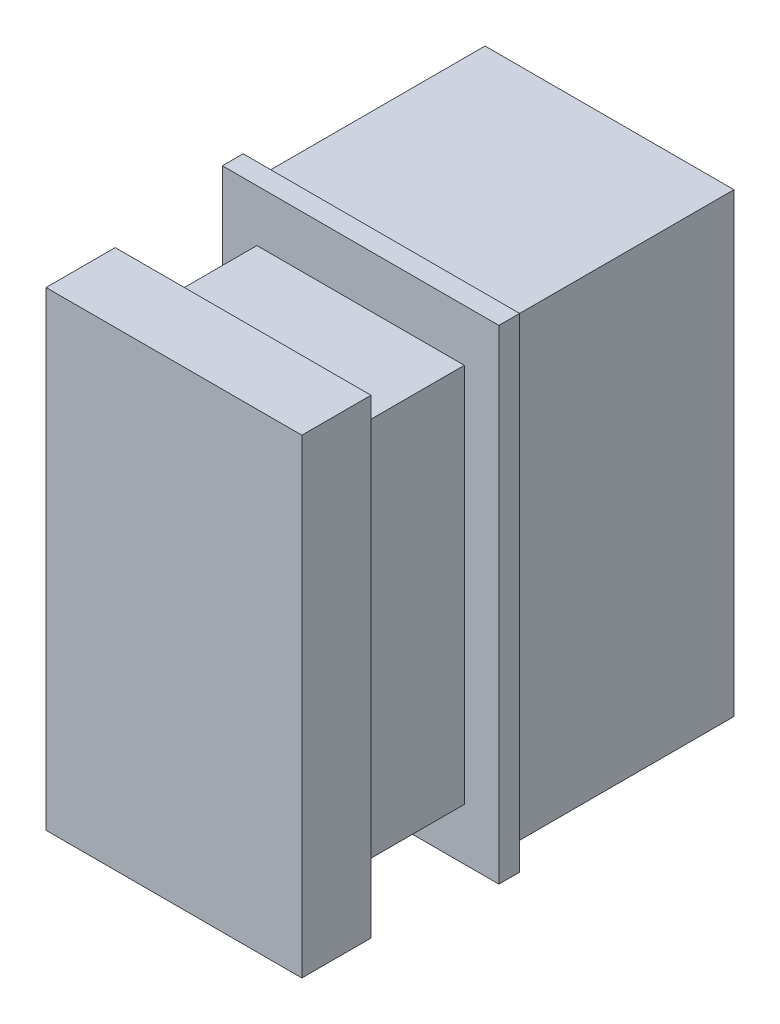
SolidWorks part; units mm, degrees
ref_plane "Piano frontale" through (0, 0, 0) normal (0, 0, 1) x (1, 0, 0)
ref_plane "Piano superiore" through (0, 0, 0) normal (0, 1, 0) x (1, 0, 0)
ref_plane "Piano destro" through (0, 0, 0) normal (1, 0, 0) x (0, 0, -1)
sketch "Schizzo1" plane through (0, 0, 0) normal (0, 0, 1) x (1, 0, 0)
  line L5 (0, 0) -> (4, 0)
  line L6 (0, 0) -> (0, 7)
  line L7 (0, 7) -> (4, 7)
  line L8 (4, 0) -> (4, 7)
  dimension "D1" = 4
  dimension "D2" = 7
extrude "Estrusione-Estrusione1" add sketch "Schizzo1" along normal blind 0.3
sketch "Schizzo2" plane through (0, 0, 0) normal (0, 0, 1) x (1, 0, 0)
  line L0 (0, 0) -> (4, 0) construction
  line L1 (0.2, 6.8) -> (3.8, 6.8)
  line L2 (0.2, 6.8) -> (0.2, 0.2)
  line L3 (0.2, 0.2) -> (3.8, 0.2)
  line L4 (3.8, 6.8) -> (3.8, 0.2)
  line L5 (4, 0) -> (4, 7) construction
  line L6 (4, 7) -> (0, 7) construction
  line L7 (0, 7) -> (0, 0) construction
  line L8 (0, 0) -> (4, 0)
  line L9 (4, 0) -> (4, 7)
  line L10 (4, 7) -> (0, 7)
  line L11 (0, 7) -> (0, 0)
  dimension "D1" = 0.2
  dimension "D2" = 0.2
  dimension "D3" = 0.2
  dimension "D4" = 0.2
extrude "Estrusione-Estrusione2" add sketch "Schizzo2" against normal blind 3.3 contours L2 L1 L4 L3
sketch "Schizzo3" plane through (0, 0, 0) normal (0, 0, 1) x (1, 0, 0)
  line L0 (0.2, 6.8) -> (3.8, 6.8) construction
  line L1 (3.6, 6.6) -> (0.4, 6.6)
  line L2 (3.6, 6.6) -> (3.6, 0.4)
  line L3 (3.6, 0.4) -> (0.4, 0.4)
  line L4 (0.4, 6.6) -> (0.4, 0.4)
  line L5 (0.2, 0.2) -> (3.8, 0.2) construction
  line L6 (3.8, 6.8) -> (3.8, 0.2) construction
  line L7 (0.2, 6.8) -> (0.2, 0.2) construction
  dimension "D1" = 0.2
  dimension "D2" = 0.2
  dimension "D3" = 0.2
  dimension "D4" = 0.2
extrude "Taglio-Estrusione1" cut sketch "Schizzo3" against normal through all
sketch "Schizzo6" plane through (0, 0, 0) normal (0, 0, 1) x (1, 0, 0)
  line L0 (4, 3.5) -> (0, 3.5) construction
  line L1 (4, 0) -> (4, 7) construction
  line L2 (0, 7) -> (0, 0) construction
  line L3 (0, 3.5) -> (2, 3.5) construction
  line L4 (2, 3.5) -> (2, 0) construction
  line L5 (0, 0) -> (4, 0) construction
  line L6 (2, 3.5) -> (2, 7) construction
  line L7 (4, 7) -> (0, 7) construction
  line L13 (0.5, 0.75) -> (3.5, 0.75)
  line L14 (0.5, 0.75) -> (0.5, 6.25)
  line L15 (0.5, 6.25) -> (3.5, 6.25)
  line L16 (3.5, 0.75) -> (3.5, 6.25)
  line L17 (0.5, 0.75) -> (3.5, 6.25) construction
  line L18 (0.5, 6.25) -> (3.5, 0.75) construction
  dimension "D1" = 3
  dimension "D2" = 5.5
extrude "Estrusione-Estrusione3" add sketch "Schizzo6" along normal blind 2 contours L14 L13 L16 L15
sketch "Schizzo7" plane through (0, 0, 2) normal (0, 0, 1) x (1, 0, 0)
  line L0 (0.5, 6.25) -> (2, 6.25) construction
  line L1 (0.5, 6.25) -> (3.5, 6.25) construction
  line L2 (2, 6.25) -> (2, 0.75) construction
  line L3 (0.5, 0.75) -> (3.5, 0.75) construction
  line L4 (2, 0.75) -> (3.5, 0.75) construction
  line L5 (3.5, 0.75) -> (0.5, 6.25) construction
  line L6 (0.5, 6.25) -> (0.5, 0.75) construction
  line L7 (0.5, 0.75) -> (3.5, 6.25) construction
  line L9 (0.15, 6.9) -> (3.85, 6.9)
  line L10 (0.15, 6.9) -> (0.15, 0.1)
  line L11 (0.15, 0.1) -> (3.85, 0.1)
  line L12 (3.85, 6.9) -> (3.85, 0.1)
  line L13 (0.15, 6.9) -> (3.85, 0.1) construction
  line L14 (0.15, 0.1) -> (3.85, 6.9) construction
  point P13 (2, 3.5)
  dimension "D1" = 3.7
  dimension "D2" = 6.8
extrude "Estrusione-Estrusione4" add sketch "Schizzo7" along normal blind 1
